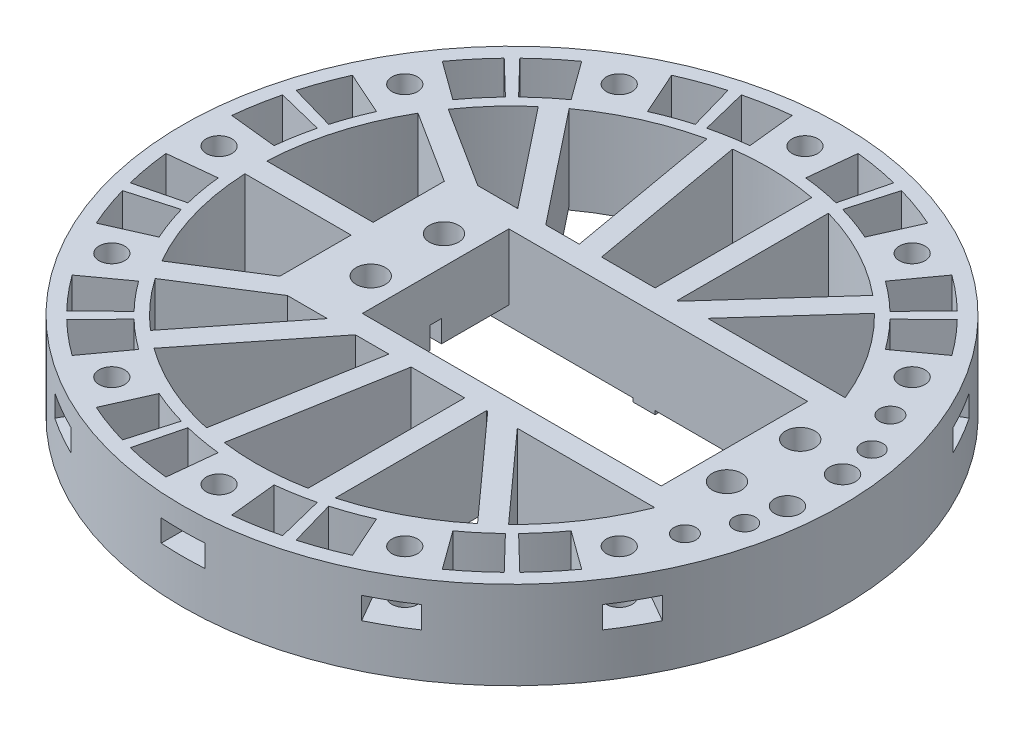
SolidWorks part; units mm, degrees
ref_plane "Front Plane" through (0, 0, 0) normal (0, 0, 1) x (1, 0, 0)
ref_plane "Top Plane" through (0, 0, 0) normal (0, 1, 0) x (1, 0, 0)
ref_plane "Right Plane" through (0, 0, 0) normal (1, 0, 0) x (0, 0, -1)
sketch "Sketch1" plane through (0, 0, 0) normal (0, 1, 0) x (1, 0, 0)
  line L0 (-43.0464, 0) -> (41.9462, 0) construction
  line L1 (0, 43.1152) -> (0, -41.8775) construction
  circle A1 centre (0, 0) radius 45
  dimension "D2" = 90
extrude "Boss-Extrude1" add sketch "Sketch1" along normal blind 12
sketch "Sketch2" plane through (0, 0, 0) normal (0, -1, 0) x (1, 0, 0)
  circle A0 centre (0, 0) radius 35
  dimension "D1" = 70
extrude "Cut-Extrude1" cut sketch "Sketch2" against normal blind 0.5
sketch "Sketch3" plane through (0, 0.5, 0) normal (0, -1, 0) x (1, 0, 0)
  line L0 (35, 0) -> (-35, 0) construction
  line L1 (0, -35) -> (0, 35) construction
  line L3 (37.5324, -10) -> (-17.4676, -10)
  line L4 (37.5324, -10) -> (37.5324, 10)
  line L5 (37.5324, 10) -> (-17.4676, 10)
  line L6 (-17.4676, -10) -> (-17.4676, 10)
  circle A0 centre (0, 0) radius 35 construction
  circle A1 centre (0, 0) radius 35 construction
  dimension "D1" = 20
  dimension "D2" = 55
  dimension "D3" = 10
  dimension "D4" = 37.5324
extrude "Cut-Extrude2" cut sketch "Sketch3" against normal blind 2.5 and the other way up to next
sketch "Sketch4" plane through (0, 3, 0) normal (0, -1, 0) x (1, 0, 0)
  line L0 (37.5324, 0) -> (-17.4676, 0) construction
  line L1 (37.5324, 10) -> (37.5324, -10) construction
  line L2 (-17.4676, 10) -> (-17.4676, -10) construction
  line L3 (0, -10) -> (0, 10) construction
  line L4 (-17.4676, -10) -> (33.541, -10) construction
  line L5 (33.541, 10) -> (-17.4676, 10) construction
  line L7 (30.3722, -10) -> (-10.4278, -10)
  line L8 (30.3722, -10) -> (30.3722, 10)
  line L9 (30.3722, 10) -> (-10.4278, 10)
  line L10 (-10.4278, -10) -> (-10.4278, 10)
  dimension "D1" = 20
  dimension "D2" = 40.8
  dimension "D3" = 30.3722
  dimension "D4" = 10
extrude "Cut-Extrude3" cut sketch "Sketch4" against normal blind 9
sketch "Sketch8" plane through (0, 0.5, 0) normal (0, -1, 0) x (1, 0, 0)
  line L0 (-17.4676, 0) -> (-35, 0) construction
  line L1 (-17.4676, 10) -> (-17.4676, -10) construction
  line L2 (8.0367, 10) -> (8.0367, 34.0648) construction
  line L3 (33.541, 10) -> (-17.4676, 10) construction
  line L4 (8.0367, -10) -> (8.0367, -29.3194) construction
  line L5 (-17.4676, -10) -> (33.541, -10) construction
  line L6 (6.5367, 10) -> (6.5367, 34.3842)
  line L7 (9.5367, 10) -> (9.5367, 33.6757)
  line L8 (9.5367, 10) -> (6.5367, 10)
  line L9 (9.5367, -10) -> (6.5367, -10)
  line L10 (6.5367, -10) -> (6.5367, -34.3842)
  line L11 (9.5367, -10) -> (9.5367, -33.6757)
  line L12 (-17.4676, 1.5) -> (-34.9678, 1.5)
  line L13 (-17.4676, -1.5) -> (-34.9678, -1.5)
  line L14 (-17.4676, 1.5) -> (-17.4676, -1.5)
  arc A0 (33.541, 10) -> (33.541, -10) centre (0, 0) ccw construction
  arc A1 (9.5367, 33.6757) -> (6.5367, 34.3842) centre (7.9531, 33.6757) ccw
  arc A2 (9.5367, -33.6757) -> (6.5367, -34.3842) centre (7.9531, -33.6757) cw
  arc A3 (-34.9678, 1.5) -> (-34.9678, -1.5) centre (-34.9678, 0) ccw
  dimension "D3" = 1.5
  dimension "D1" = 1.5
  dimension "D2" = 1.5
  dimension "D4" = 1.5
extrude "Boss-Extrude2" add sketch "Sketch8" along normal through all
sketch "Sketch15" plane through (0, 0, -1.5) normal (0, 0, -1) x (-1, 0, 0)
  line L0 (34.9678, 0) -> (17.4676, 0.5)
  line L1 (17.4676, 0.5) -> (17.4676, 0)
  line L3 (17.4676, 0) -> (34.9678, 0)
sketch "Sketch16" plane through (0, 3, 0) normal (0, -1, 0) x (1, 0, 0)
  line L0 (-17.4676, 0) -> (37.5324, 0) construction
  line L1 (-17.4676, 10) -> (-17.4676, -10) construction
  line L2 (37.5324, -10) -> (37.5324, 10) construction
  line L3 (30.3722, -0.8) -> (37.5324, -0.8)
  line L4 (-10.4278, -0.8) -> (-17.4676, -0.8)
  line L5 (-10.4278, 10) -> (-10.4278, -10) construction
  line L6 (-10.4278, 0.8) -> (-17.4676, 0.8)
  line L7 (-17.4676, 0.8) -> (-17.4676, -0.8)
  line L8 (-10.4278, 0.8) -> (-10.4278, -0.8)
  line L9 (30.3722, -10) -> (30.3722, 10) construction
  line L10 (30.3722, 0.8) -> (37.5324, 0.8)
  line L11 (37.5324, 0.8) -> (37.5324, -0.8)
  line L12 (30.3722, 0.8) -> (30.3722, -0.8)
  dimension "D1" = 0.8
extrude "Cut-Extrude10" cut sketch "Sketch16" against normal blind 3
sketch "Sketch27" plane through (0, 0, 0) normal (0, -1, 0) x (1, 0, 0)
  line L0 (0, 0) -> (0, -53.17) construction
  line L1 (0, 0) -> (47.7582, -27.5732) construction
  line L3 (31.641, -18.2679) -> (31.641, -21.7321) construction
  line L4 (31.641, -21.7321) -> (34.641, -23.4641) construction
  line L5 (34.641, -23.4641) -> (37.641, -21.7321) construction
  line L6 (37.641, -21.7321) -> (37.641, -18.2679) construction
  line L7 (37.641, -18.2679) -> (34.641, -16.5359) construction
  line L8 (34.641, -16.5359) -> (31.641, -18.2679) construction
  circle A0 centre (0, 0) radius 40 construction
  circle A1 centre (34.641, -20) radius 1.75
  circle A2 centre (0, 0) radius 35 construction
  circle A3 centre (34.641, -20) radius 3 construction
  circle A4 centre (20, -34.641) radius 1.75
  circle A5 centre (0, -40) radius 1.75
  circle A6 centre (-20, -34.641) radius 1.75
  circle A7 centre (-34.641, -20) radius 1.75
  circle A8 centre (-40, 0) radius 1.75
  circle A9 centre (-34.641, 20) radius 1.75
  circle A10 centre (-20, 34.641) radius 1.75
  circle A11 centre (0, 40) radius 1.75
  circle A12 centre (20, 34.641) radius 1.75
  circle A13 centre (34.641, 20) radius 1.75
  circle A15 centre (40, 0) radius 1.75 [skipped]
  point P28 (0, 0)
  point P41 (0, 0)
  dimension "D1" = 80
  dimension "D3" = 3.5
  dimension "D4" = 70
  dimension "D5" = 6
  dimension "D6" = 12
  dimension "D2" = 60
extrude "Cut-Extrude15" cut sketch "Sketch27" against normal through all
ref_plane "Plane1" through (0, 9, 0) normal (0, 1, 0) x (1, 0, 0)
sketch "Sketch28" plane through (0, 9, 0) normal (0, 1, 0) x (1, 0, 0)
  line L0 (0, 0) -> (-54.493, 0) construction
  line L1 (-31.641, 18.2679) -> (-31.641, 21.7321)
  line L2 (-36.5359, 0) -> (-38.2679, 3)
  line L3 (-38.2679, 3) -> (-44.8999, 3)
  line L4 (-31.641, 21.7321) -> (-37.3844, 25.048)
  line L5 (-40.3844, 19.8519) -> (-34.641, 16.5359)
  line L6 (-44.8999, -3) -> (-38.2679, -3)
  line L7 (-38.2679, -3) -> (-36.5359, 0)
  line L8 (-43.4641, 0) -> (-42.5981, -1.5) [skipped]
  line L9 (-41.7321, 3) -> (-42.5981, 1.5) [skipped]
  line L10 (-34.641, 16.5359) -> (-31.641, 18.2679)
  line L11 (-18.2679, 31.641) -> (-16.5359, 34.641)
  line L12 (-16.5359, 34.641) -> (-19.8519, 40.3844)
  line L13 (-25.048, 37.3844) -> (-21.7321, 31.641)
  line L14 (-21.7321, 31.641) -> (-18.2679, 31.641)
  line L15 (0, 36.5359) -> (3, 38.2679)
  line L16 (3, 38.2679) -> (3, 44.8999)
  line L17 (-3, 44.8999) -> (-3, 38.2679)
  line L18 (-3, 38.2679) -> (0, 36.5359)
  line L19 (18.2679, 31.641) -> (21.7321, 31.641)
  line L20 (21.7321, 31.641) -> (25.048, 37.3844)
  line L21 (19.8519, 40.3844) -> (16.5359, 34.641)
  line L22 (16.5359, 34.641) -> (18.2679, 31.641)
  line L23 (31.641, 18.2679) -> (34.641, 16.5359)
  line L24 (34.641, 16.5359) -> (40.3844, 19.8519)
  line L25 (37.3844, 25.048) -> (31.641, 21.7321)
  line L26 (31.641, 21.7321) -> (31.641, 18.2679)
  line L31 (31.641, -18.2679) -> (31.641, -21.7321)
  line L32 (31.641, -21.7321) -> (37.3844, -25.048)
  line L33 (40.3844, -19.8519) -> (34.641, -16.5359)
  line L34 (34.641, -16.5359) -> (31.641, -18.2679)
  line L35 (18.2679, -31.641) -> (16.5359, -34.641)
  line L36 (16.5359, -34.641) -> (19.8519, -40.3844)
  line L37 (25.048, -37.3844) -> (21.7321, -31.641)
  line L38 (21.7321, -31.641) -> (18.2679, -31.641)
  line L39 (0, -36.5359) -> (-3, -38.2679)
  line L40 (-3, -38.2679) -> (-3, -44.8999)
  line L41 (3, -44.8999) -> (3, -38.2679)
  line L42 (3, -38.2679) -> (0, -36.5359)
  line L43 (-18.2679, -31.641) -> (-21.7321, -31.641)
  line L44 (-21.7321, -31.641) -> (-25.048, -37.3844)
  line L45 (-19.8519, -40.3844) -> (-16.5359, -34.641)
  line L46 (-16.5359, -34.641) -> (-18.2679, -31.641)
  line L47 (-31.641, -18.2679) -> (-34.641, -16.5359)
  line L48 (-34.641, -16.5359) -> (-40.3844, -19.8519)
  line L49 (-37.3844, -25.048) -> (-31.641, -21.7321)
  line L50 (-31.641, -21.7321) -> (-31.641, -18.2679)
  line L51 (36.5359, 0) -> (38.2679, -3) [skipped]
  line L52 (38.2679, -3) -> (44.8999, -3) [skipped]
  line L53 (44.8999, 3) -> (38.2679, 3) [skipped]
  line L54 (38.2679, 3) -> (36.5359, 0) [skipped]
  arc A0 (-44.8999, 3) -> (-44.8999, -3) centre (0, 0) ccw
  circle A1 centre (-40, 0) radius 3 construction
  arc A2 (-37.3844, 25.048) -> (-40.3844, 19.8519) centre (0, 0) ccw
  circle A3 centre (-34.641, 20) radius 3 construction
  arc A4 (-19.8519, 40.3844) -> (-25.048, 37.3844) centre (0, 0) ccw
  circle A5 centre (-20, 34.641) radius 3 construction
  arc A6 (3, 44.8999) -> (-3, 44.8999) centre (0, 0) ccw
  circle A7 centre (0, 40) radius 3 construction
  arc A8 (25.048, 37.3844) -> (19.8519, 40.3844) centre (0, 0) ccw
  circle A9 centre (20, 34.641) radius 3 construction
  arc A10 (40.3844, 19.8519) -> (37.3844, 25.048) centre (0, 0) ccw
  circle A11 centre (34.641, 20) radius 3 construction
  arc A14 (37.3844, -25.048) -> (40.3844, -19.8519) centre (0, 0) ccw
  circle A15 centre (34.641, -20) radius 3 construction
  arc A16 (19.8519, -40.3844) -> (25.048, -37.3844) centre (0, 0) ccw
  circle A17 centre (20, -34.641) radius 3 construction
  arc A18 (-3, -44.8999) -> (3, -44.8999) centre (0, 0) ccw
  circle A19 centre (0, -40) radius 3 construction
  arc A20 (-25.048, -37.3844) -> (-19.8519, -40.3844) centre (0, 0) ccw
  circle A21 centre (-20, -34.641) radius 3 construction
  arc A22 (-40.3844, -19.8519) -> (-37.3844, -25.048) centre (0, 0) ccw
  circle A23 centre (-34.641, -20) radius 3 construction
  arc A24 (44.8999, -3) -> (44.8999, 3) centre (0, 0) ccw [skipped]
  circle A25 centre (40, 0) radius 3 construction
  point P94 (0, 0)
  dimension "D1" = 90
  dimension "D2" = 6
  dimension "D3" = 12
extrude "Cut-Extrude17" cut sketch "Sketch28" against normal blind 3
sketch "Sketch29" plane through (0, 0.5, 0) normal (0, -1, 0) x (1, 0, 0)
  line L0 (32.4962, -13) -> (13.7255, -13)
  line L1 (9.5367, -33.6757) -> (9.5367, -10) construction
  line L2 (9.5367, -13) -> (9.5367, -33.6757)
  line L3 (9.5367, -10) -> (33.541, -10) construction
  line L4 (6.5367, -13) -> (-0.7691, -13)
  line L5 (6.5367, -10) -> (6.5367, -34.3842) construction
  line L6 (-20.4676, -11.223) -> (-20.4676, -1.5)
  line L7 (-34.9678, -1.5) -> (-17.4676, -1.5) construction
  line L8 (-20.4676, -1.5) -> (-34.9678, -1.5)
  line L9 (-17.4676, -0.8) -> (-17.4676, -10) construction
  line L10 (32.4962, 13) -> (13.7255, 13)
  line L11 (9.5367, 10) -> (9.5367, 33.6757) construction
  line L12 (9.5367, 13) -> (9.5367, 33.6757)
  line L13 (-7.5493, 34.1761) -> (-3.8154, 13)
  line L14 (6.5367, 13) -> (-0.7691, 13)
  line L15 (6.5367, 34.3842) -> (6.5367, 10) construction
  line L16 (-20.4676, 11.223) -> (-20.4676, 1.5)
  line L17 (-17.4676, 1.5) -> (-34.9678, 1.5) construction
  line L18 (-20.4676, 1.5) -> (-34.9678, 1.5)
  line L19 (6.5367, 13) -> (6.5367, 34.3842)
  line L20 (6.5367, -34.3842) -> (6.5367, -13)
  line L21 (0, 0) -> (-21.7353, -27.4331) construction
  line L22 (-20.5397, -28.3394) -> (-8.3862, -13)
  line L23 (-22.8911, -26.4764) -> (-12.2137, -13)
  line L24 (0, 0) -> (-20.4676, -13) construction
  line L25 (-17.6698, -13) -> (-28.713, -20.0141)
  line L26 (-20.4676, -11.223) -> (-30.3215, -17.4817)
  line L27 (0, 0) -> (-35, 0) construction
  line L28 (-20.4676, 11.223) -> (-30.3215, 17.4817)
  line L29 (-17.6698, 13) -> (-28.713, 20.0141)
  line L30 (-22.8911, 26.4764) -> (-12.2137, 13)
  line L31 (-20.5397, 28.3394) -> (-8.3862, 13)
  line L32 (-12.2137, 13) -> (-17.6698, 13)
  line L33 (0, 0) -> (-6.0777, -34.4683) construction
  line L34 (-4.5949, -34.6971) -> (-0.7691, -13)
  line L35 (-7.5493, -34.1761) -> (-3.8154, -13)
  line L36 (-3.8154, -13) -> (-17.6698, -13)
  line L37 (-4.5949, 34.6971) -> (-0.7691, 13)
  line L38 (-3.8154, 13) -> (-8.3862, 13)
  line L39 (0, 0) -> (23.4214, -26.0084) construction
  line L40 (9.6883, -13) -> (22.2852, -26.9883)
  line L41 (13.7255, -13) -> (24.5145, -24.9808)
  line L42 (13.7255, 13) -> (24.5145, 24.9808)
  line L43 (9.6883, 13) -> (22.2852, 26.9883)
  line L44 (9.6883, -13) -> (9.5367, -13)
  line L45 (9.6883, 13) -> (9.5367, 13)
  arc A0 (9.5367, -33.6757) -> (22.2852, -26.9883) centre (0, 0) ccw
  arc A1 (6.5367, 34.3842) -> (-4.5949, 34.6971) centre (0, 0) ccw
  arc A2 (32.4962, 13) -> (24.5145, 24.9808) centre (0, 0) ccw
  arc A3 (-34.9678, -1.5) -> (-30.3215, -17.4817) centre (0, 0) ccw
  circle A4 centre (0, 0) radius 35 construction
  arc A5 (-7.5493, 34.1761) -> (-20.5397, 28.3394) centre (0, 0) ccw
  arc A6 (-4.5949, -34.6971) -> (6.5367, -34.3842) centre (0, 0) ccw
  arc A7 (-20.5397, -28.3394) -> (-7.5493, -34.1761) centre (0, 0) ccw
  arc A8 (-28.713, -20.0141) -> (-22.8911, -26.4764) centre (0, 0) ccw
  arc A9 (-30.3215, 17.4817) -> (-34.9678, 1.5) centre (0, 0) ccw
  arc A10 (-22.8911, 26.4764) -> (-28.713, 20.0141) centre (0, 0) ccw
  arc A11 (24.5145, -24.9808) -> (32.4962, -13) centre (0, 0) ccw
  arc A12 (22.2852, 26.9883) -> (9.5367, 33.6757) centre (0, 0) ccw
  point P11 (21.5389, -10)
  point P23 (-17.4676, -5.4)
  line M3 (-17.4676, -1.5) -> (-34.9678, -1.5)
  arc M4 (-34.9678, -1.5) -> (6.5367, -34.3842) centre (0, 0) ccw
  line M5 (6.5367, -34.3842) -> (6.5367, -10)
  dimension "D1" = 1.5
  dimension "D2" = 3
  dimension "D3" = 3
  dimension "D4" = 80
  dimension "D5" = 1.5
  dimension "D6" = 1.5
  dimension "D7" = 1.5
sketch "Sketch30" plane through (0, 0, 0) normal (0, -1, 0) x (1, 0, 0)
  line L0 (0, 0) -> (0, -40) construction
  line L1 (-16.5359, -34.641) -> (-18.2679, -31.641) construction
  line L2 (0, -36.5359) -> (-3, -38.2679) construction
  line L3 (-3, -38.2679) -> (-3, -41.7321) construction
  line L4 (-3, -41.7321) -> (0, -43.4641) construction
  line L5 (0, -43.4641) -> (3, -41.7321) construction
  line L6 (3, -41.7321) -> (3, -38.2679) construction
  line L7 (3, -38.2679) -> (0, -36.5359) construction
  line L8 (-18.2679, -31.641) -> (-21.7321, -31.641) construction
  line L9 (-21.7321, -31.641) -> (-23.4641, -34.641) construction
  line L10 (-23.4641, -34.641) -> (-21.7321, -37.641) construction
  line L11 (-21.7321, -37.641) -> (-18.2679, -37.641) construction
  line L12 (-18.2679, -37.641) -> (-16.5359, -34.641) construction
  line L13 (-31.641, -21.7321) -> (-31.641, -18.2679) construction
  line L14 (-31.641, -18.2679) -> (-34.641, -16.5359) construction
  line L15 (-34.641, -16.5359) -> (-37.641, -18.2679) construction
  line L16 (-37.641, -18.2679) -> (-37.641, -21.7321) construction
  line L17 (-37.641, -21.7321) -> (-34.641, -23.4641) construction
  line L18 (-34.641, -23.4641) -> (-31.641, -21.7321) construction
  line L19 (-38.2679, -3) -> (-36.5359, 0) construction
  line L20 (-36.5359, 0) -> (-38.2679, 3) construction
  line L21 (-38.2679, 3) -> (-41.7321, 3) construction
  line L22 (-41.7321, 3) -> (-43.4641, 0) construction
  line L23 (-43.4641, 0) -> (-41.7321, -3) construction
  line L24 (-41.7321, -3) -> (-38.2679, -3) construction
  line L25 (-34.641, 16.5359) -> (-31.641, 18.2679) construction
  line L26 (-31.641, 18.2679) -> (-31.641, 21.7321) construction
  line L27 (-31.641, 21.7321) -> (-34.641, 23.4641) construction
  line L28 (-34.641, 23.4641) -> (-37.641, 21.7321) construction
  line L29 (-37.641, 21.7321) -> (-37.641, 18.2679) construction
  line L30 (-37.641, 18.2679) -> (-34.641, 16.5359) construction
  line L31 (-21.7321, 31.641) -> (-18.2679, 31.641) construction
  line L32 (-18.2679, 31.641) -> (-16.5359, 34.641) construction
  line L33 (-16.5359, 34.641) -> (-18.2679, 37.641) construction
  line L34 (-18.2679, 37.641) -> (-21.7321, 37.641) construction
  line L35 (-21.7321, 37.641) -> (-23.4641, 34.641) construction
  line L36 (-23.4641, 34.641) -> (-21.7321, 31.641) construction
  line L37 (-3, 38.2679) -> (0, 36.5359) construction
  line L38 (0, 36.5359) -> (3, 38.2679) construction
  line L39 (3, 38.2679) -> (3, 41.7321) construction
  line L40 (3, 41.7321) -> (0, 43.4641) construction
  line L41 (0, 43.4641) -> (-3, 41.7321) construction
  line L42 (-3, 41.7321) -> (-3, 38.2679) construction
  line L43 (16.5359, 34.641) -> (18.2679, 31.641) construction
  line L44 (18.2679, 31.641) -> (21.7321, 31.641) construction
  line L45 (21.7321, 31.641) -> (23.4641, 34.641) construction
  line L46 (23.4641, 34.641) -> (21.7321, 37.641) construction
  line L47 (21.7321, 37.641) -> (18.2679, 37.641) construction
  line L48 (18.2679, 37.641) -> (16.5359, 34.641) construction
  line L49 (31.641, 21.7321) -> (31.641, 18.2679) construction
  line L50 (31.641, 18.2679) -> (34.641, 16.5359) construction
  line L51 (34.641, 16.5359) -> (37.641, 18.2679) construction
  line L52 (37.641, 18.2679) -> (37.641, 21.7321) construction
  line L53 (37.641, 21.7321) -> (34.641, 23.4641) construction
  line L54 (34.641, 23.4641) -> (31.641, 21.7321) construction
  line L61 (34.641, -16.5359) -> (31.641, -18.2679) construction
  line L62 (31.641, -18.2679) -> (31.641, -21.7321) construction
  line L63 (31.641, -21.7321) -> (34.641, -23.4641) construction
  line L64 (34.641, -23.4641) -> (37.641, -21.7321) construction
  line L65 (37.641, -21.7321) -> (37.641, -18.2679) construction
  line L66 (37.641, -18.2679) -> (34.641, -16.5359) construction
  line L67 (21.7321, -31.641) -> (18.2679, -31.641) construction
  line L68 (18.2679, -31.641) -> (16.5359, -34.641) construction
  line L69 (16.5359, -34.641) -> (18.2679, -37.641) construction
  line L70 (18.2679, -37.641) -> (21.7321, -37.641) construction
  line L71 (21.7321, -37.641) -> (23.4641, -34.641) construction
  line L72 (23.4641, -34.641) -> (21.7321, -31.641) construction
  line L73 (-4.4947, -42.7644) -> (-3.8153, -36.3)
  line L74 (-8.8301, -35.4158) -> (-10.4026, -41.7227)
  line L75 (0, 0) -> (-12.6247, -47.1159) construction
  line L76 (-10.0608, -35.0861) -> (-11.8524, -41.3343)
  line L77 (-17.4897, -39.2825) -> (-14.8459, -33.3444)
  line L78 (-25.2748, -34.7877) -> (-21.4542, -29.5291)
  line L79 (-25.355, -26.2559) -> (-29.8703, -30.9316)
  line L80 (-26.2559, -25.355) -> (-30.9316, -29.8703)
  line L81 (-34.7877, -25.2748) -> (-29.5291, -21.4542)
  line L82 (-39.2825, -17.4897) -> (-33.3444, -14.8459)
  line L83 (-35.0861, -10.0608) -> (-41.3343, -11.8524)
  line L84 (-35.4158, -8.8301) -> (-41.7227, -10.4026)
  line L85 (-42.7644, -4.4947) -> (-36.3, -3.8153)
  line L86 (-42.7644, 4.4947) -> (-36.3, 3.8153)
  line L87 (-35.4158, 8.8301) -> (-41.7227, 10.4026)
  line L88 (-35.0861, 10.0608) -> (-41.3343, 11.8524)
  line L89 (-39.2825, 17.4897) -> (-33.3444, 14.8459)
  line L90 (-34.7877, 25.2748) -> (-29.5291, 21.4542)
  line L91 (-26.2559, 25.355) -> (-30.9316, 29.8703)
  line L92 (-25.355, 26.2559) -> (-29.8703, 30.9316)
  line L93 (-25.2748, 34.7877) -> (-21.4542, 29.5291)
  line L94 (-17.4897, 39.2825) -> (-14.8459, 33.3444)
  line L95 (-10.0608, 35.0861) -> (-11.8524, 41.3343)
  line L96 (-8.8301, 35.4158) -> (-10.4026, 41.7227)
  line L97 (-4.4947, 42.7644) -> (-3.8153, 36.3)
  line L98 (4.4947, 42.7644) -> (3.8153, 36.3)
  line L99 (8.8301, 35.4158) -> (10.4026, 41.7227)
  line L100 (10.0608, 35.0861) -> (11.8524, 41.3343)
  line L101 (17.4897, 39.2825) -> (14.8459, 33.3444)
  line L102 (25.2748, 34.7877) -> (21.4542, 29.5291)
  line L103 (25.355, 26.2559) -> (29.8703, 30.9316)
  line L104 (26.2559, 25.355) -> (30.9316, 29.8703)
  line L105 (34.7877, 25.2748) -> (29.5291, 21.4542)
  line L106 (0, 0) -> (45, 0) construction
  line L114 (34.7877, -25.2748) -> (29.5291, -21.4542)
  line L115 (26.2559, -25.355) -> (30.9316, -29.8703)
  line L116 (25.355, -26.2559) -> (29.8703, -30.9316)
  line L117 (25.2748, -34.7877) -> (21.4542, -29.5291)
  line L118 (17.4897, -39.2825) -> (14.8459, -33.3444)
  line L119 (10.0608, -35.0861) -> (11.8524, -41.3343)
  line L120 (8.8301, -35.4158) -> (10.4026, -41.7227)
  line L121 (4.4947, -42.7644) -> (3.8153, -36.3)
  line L122 (35.0861, -10.0608) -> (41.3343, -11.8524) [skipped]
  line L123 (39.2825, -17.4897) -> (33.3444, -14.8459) [skipped]
  line L124 (42.7644, -4.4947) -> (36.3, -3.8153) [skipped]
  line L125 (35.4158, -8.8301) -> (41.7227, -10.4026) [skipped]
  line L126 (42.7644, 4.4947) -> (36.3, 3.8153) [skipped]
  line L127 (35.4158, 8.8301) -> (41.7227, 10.4026) [skipped]
  line L128 (35.0861, 10.0608) -> (41.3343, 11.8524) [skipped]
  line L129 (39.2825, 17.4897) -> (33.3444, 14.8459) [skipped]
  line L130 (38.2679, 3) -> (36.5359, 0) construction
  line L131 (36.5359, 0) -> (38.2679, -3) construction
  line L132 (38.2679, -3) -> (41.7321, -3) construction
  line L133 (41.7321, -3) -> (43.4641, 0) construction
  line L134 (43.4641, 0) -> (41.7321, 3) construction
  line L135 (41.7321, 3) -> (38.2679, 3) construction
  circle A0 centre (0, -40) radius 3 construction
  arc A1 (-3.8153, -36.3) -> (-8.8301, -35.4158) centre (0, 0) cw
  arc A2 (-4.4947, -42.7644) -> (-10.4026, -41.7227) centre (0, 0) cw
  arc A3 (-14.8459, -33.3444) -> (-10.0608, -35.0861) centre (0, 0) ccw
  arc A4 (-17.4897, -39.2825) -> (-11.8524, -41.3343) centre (0, 0) ccw
  arc A5 (-25.2748, -34.7877) -> (-29.8703, -30.9316) centre (0, 0) cw
  arc A6 (-21.4542, -29.5291) -> (-25.355, -26.2559) centre (0, 0) cw
  arc A7 (-34.7877, -25.2748) -> (-30.9316, -29.8703) centre (0, 0) ccw
  arc A8 (-29.5291, -21.4542) -> (-26.2559, -25.355) centre (0, 0) ccw
  arc A9 (-39.2825, -17.4897) -> (-41.3343, -11.8524) centre (0, 0) cw
  arc A10 (-33.3444, -14.8459) -> (-35.0861, -10.0608) centre (0, 0) cw
  arc A11 (-42.7644, -4.4947) -> (-41.7227, -10.4026) centre (0, 0) ccw
  arc A12 (-36.3, -3.8153) -> (-35.4158, -8.8301) centre (0, 0) ccw
  arc A13 (-42.7644, 4.4947) -> (-41.7227, 10.4026) centre (0, 0) cw
  arc A14 (-36.3, 3.8153) -> (-35.4158, 8.8301) centre (0, 0) cw
  arc A15 (-39.2825, 17.4897) -> (-41.3343, 11.8524) centre (0, 0) ccw
  arc A16 (-33.3444, 14.8459) -> (-35.0861, 10.0608) centre (0, 0) ccw
  arc A17 (-34.7877, 25.2748) -> (-30.9316, 29.8703) centre (0, 0) cw
  arc A18 (-29.5291, 21.4542) -> (-26.2559, 25.355) centre (0, 0) cw
  arc A19 (-25.2748, 34.7877) -> (-29.8703, 30.9316) centre (0, 0) ccw
  arc A20 (-21.4542, 29.5291) -> (-25.355, 26.2559) centre (0, 0) ccw
  arc A21 (-17.4897, 39.2825) -> (-11.8524, 41.3343) centre (0, 0) cw
  arc A22 (-14.8459, 33.3444) -> (-10.0608, 35.0861) centre (0, 0) cw
  arc A23 (-4.4947, 42.7644) -> (-10.4026, 41.7227) centre (0, 0) ccw
  arc A24 (-3.8153, 36.3) -> (-8.8301, 35.4158) centre (0, 0) ccw
  arc A25 (4.4947, 42.7644) -> (10.4026, 41.7227) centre (0, 0) cw
  arc A26 (3.8153, 36.3) -> (8.8301, 35.4158) centre (0, 0) cw
  arc A27 (17.4897, 39.2825) -> (11.8524, 41.3343) centre (0, 0) ccw
  arc A28 (14.8459, 33.3444) -> (10.0608, 35.0861) centre (0, 0) ccw
  arc A29 (25.2748, 34.7877) -> (29.8703, 30.9316) centre (0, 0) cw
  arc A30 (21.4542, 29.5291) -> (25.355, 26.2559) centre (0, 0) cw
  arc A31 (34.7877, 25.2748) -> (30.9316, 29.8703) centre (0, 0) ccw
  arc A32 (29.5291, 21.4542) -> (26.2559, 25.355) centre (0, 0) ccw
  circle A33 centre (0, 0) radius 45 construction
  circle A34 centre (37.641, 14.0313) radius 1.4955
  circle A35 centre (40.4601, 8.7092) radius 1.4636
  circle A36 centre (41.376, 3.763) radius 1.7581
  circle A37 centre (37.641, -14.0313) radius 1.4955
  circle A38 centre (40.4601, -8.7092) radius 1.4636
  circle A39 centre (41.376, -3.763) radius 1.7581
  arc A41 (34.7877, -25.2748) -> (30.9316, -29.8703) centre (0, 0) cw
  arc A42 (29.5291, -21.4542) -> (26.2559, -25.355) centre (0, 0) cw
  arc A43 (25.2748, -34.7877) -> (29.8703, -30.9316) centre (0, 0) ccw
  arc A44 (21.4542, -29.5291) -> (25.355, -26.2559) centre (0, 0) ccw
  arc A45 (17.4897, -39.2825) -> (11.8524, -41.3343) centre (0, 0) cw
  arc A46 (14.8459, -33.3444) -> (10.0608, -35.0861) centre (0, 0) cw
  arc A47 (4.4947, -42.7644) -> (10.4026, -41.7227) centre (0, 0) ccw
  arc A48 (3.8153, -36.3) -> (8.8301, -35.4158) centre (0, 0) ccw
  arc A49 (39.2825, -17.4897) -> (41.3343, -11.8524) centre (0, 0) ccw [skipped]
  arc A50 (33.3444, -14.8459) -> (35.0861, -10.0608) centre (0, 0) ccw [skipped]
  arc A51 (36.3, -3.8153) -> (35.4158, -8.8301) centre (0, 0) cw [skipped]
  arc A52 (42.7644, -4.4947) -> (41.7227, -10.4026) centre (0, 0) cw [skipped]
  arc A53 (36.3, 3.8153) -> (35.4158, 8.8301) centre (0, 0) ccw [skipped]
  arc A54 (42.7644, 4.4947) -> (41.7227, 10.4026) centre (0, 0) ccw [skipped]
  arc A55 (33.3444, 14.8459) -> (35.0861, 10.0608) centre (0, 0) cw [skipped]
  arc A56 (39.2825, 17.4897) -> (41.3343, 11.8524) centre (0, 0) cw [skipped]
  point P79 (0, 0)
  point P178 (0, 0)
  dimension "D1" = 6
  dimension "D4" = 43
  dimension "D6" = 36.5
  dimension "D3" = 9
  dimension "D5" = 15
  dimension "D7" = 1
  dimension "D2" = 12
  dimension "D8" = 12
extrude "Cut-Extrude20" cut sketch "Sketch30" against normal through all
sketch "Sketch32" plane through (0, 3, 0) normal (0, -1, 0) x (1, 0, 0)
  line L0 (-17.4676, 0) -> (37.5324, 0) construction
  line L1 (-17.4676, -1.5) -> (-17.4676, 1.5) construction
  line L2 (37.5324, 10) -> (37.5324, -10) construction
  line L3 (10.0324, 0) -> (10.0324, -10) construction
  line L6 (9.5367, -10) -> (33.541, -10) construction
  circle A0 centre (-14.2876, -5) radius 2
  circle A1 centre (-14.2876, 5) radius 2
  circle A2 centre (34.3524, -5) radius 2
  circle A3 centre (34.3524, 5) radius 2
  dimension "D1" = 24.32
  dimension "D3" = 4
  dimension "D2" = 5
extrude "Cut-Extrude21" cut sketch "Sketch32" against normal through all
extrude "Cut-Extrude22" cut sketch "Sketch29" against normal blind 12 contours L28 A9 L18 L16 | L26 L6 M3 M4 | L23 L36 L25 M4 | L35 L36 L22 M4 | L34 L4 M4 M5 | L2 A0 L40 L44 | L41 A11 L0 | L10 A2 L42 | L43 A12 L12 L45 | L19 A1 L37 L14 | L13 A5 L31 L38 | L30 A10 L29 L32 region at (23.89, 0.5, -17.1237) region at (13.9029, 0.5, -24.813) region at (1.8383, 0.5, -24.6789) region at (-27.5459, 0.5, -7.8919) region at (-10.8152, 0.5, -24.1049) region at (-20.9968, 0.5, -18.9781) region at (23.89, 0.5, 17.1237) region at (13.9029, 0.5, 24.813) region at (-10.8152, 0.5, 24.1049) region at (1.8383, 0.5, 24.6789) region at (-27.5459, 0.5, 7.8919) region at (-20.9968, 0.5, 18.9781)
